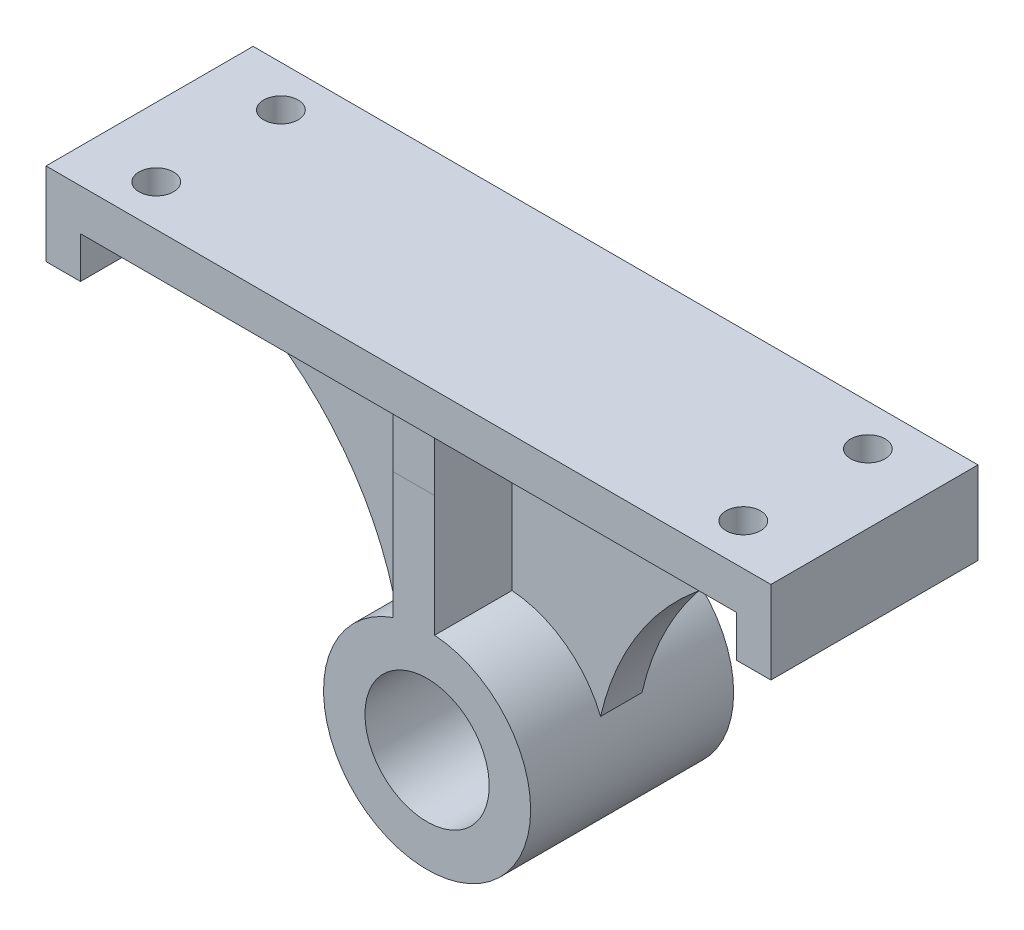
SolidWorks part; units mm, degrees
ref_plane "Front Plane" through (0, 0, 0) normal (0, 0, 1) x (1, 0, 0)
ref_plane "Top Plane" through (0, 0, 0) normal (0, 1, 0) x (1, 0, 0)
ref_plane "Right Plane" through (0, 0, 0) normal (1, 0, 0) x (0, 0, -1)
sketch "Sketch1" plane through (0, 0, 0) normal (0, 0, 1) x (1, 0, 0)
  line L0 (-266.7, 15.24) -> (-266.7, -45.72)
  line L1 (-241.3, -15.24) -> (241.3, -15.24)
  line L2 (-266.7, -15.24) -> (-266.7, 15.24)
  line L3 (-266.7, 15.24) -> (266.7, 15.24)
  line L4 (266.7, -15.24) -> (266.7, 15.24)
  line L7 (-266.7, -45.72) -> (-241.3, -45.72)
  line L8 (-241.3, -45.72) -> (-241.3, -15.24)
  line L9 (266.7, 15.24) -> (266.7, -45.72)
  line L10 (266.7, -45.72) -> (241.3, -45.72)
  line L11 (241.3, -45.72) -> (241.3, -15.24)
  point P0 (0, 0)
  dimension "D1" = 30.48
  dimension "D2" = 533.4
  dimension "D3" = 60.96
  dimension "D4" = 25.4
  dimension "D5" = 30.48
  dimension "D6" = 60.96
  dimension "D7" = 25.4
  dimension "D8" = 30.48
extrude "Boss-Extrude1" add sketch "Sketch1" against normal blind 152.4 contours L11 L10 L9 L4 L3 L0 L7 L8 L1 region at (0, -2.6504, 0)
sketch "Sketch3" plane through (0, 15.24, 0) normal (0, 1, 0) x (1, 0, 0)
  line L0 (-266.7, 0) -> (-215.9722, 0)
  line L1 (-266.7, 0) -> (266.7, 0) construction
  line L2 (-266.7, 152.4) -> (-266.7, 122.1057)
  line L3 (-266.7, 152.4) -> (-266.7, 0) construction
  line L4 (-266.7, 0) -> (-266.7, 30.4144)
  line L8 (0, 0) -> (0, 152.4) construction
  line L9 (-266.7, 152.4) -> (266.7, 152.4) construction
  circle A0 centre (-215.9722, 122.1057) radius 12.7
  circle A1 centre (-215.9722, 30.4144) radius 12.7
  circle A2 centre (215.9722, 30.4144) radius 12.7
  circle A3 centre (215.9722, 122.1057) radius 12.7
  point P23 (0, 0)
  point P24 (0, 0)
  dimension "D1" = 25.4
  dimension "D2" = 25.4
extrude "Cut-Extrude1" cut sketch "Sketch3" against normal blind 40.64 contours A3 | A2 | A0 | A1 region at (-215.9722, 15.24, -122.1057) region at (-215.9722, 15.24, -30.4144) region at (215.9722, 15.24, -30.4144) region at (215.9722, 15.24, -122.1057)
sketch "Sketch4" plane through (0, -15.24, 0) normal (0, -1, 0) x (1, 0, 0)
  line L0 (0, 0) -> (0, -152.4) construction
  line L1 (-182.88, -91.44) -> (182.88, -91.44)
  line L5 (-241.3, 0) -> (241.3, 0) construction
  line L6 (-241.3, -152.4) -> (241.3, -152.4) construction
  line L7 (0, -76.2) -> (0, -60.96)
  line L8 (0, -76.2) -> (0, -91.44)
  line L9 (-182.88, -60.96) -> (182.88, -60.96)
  line L11 (-182.88, -60.96) -> (-182.88, -91.44)
  line L12 (182.88, -60.96) -> (182.88, -91.44)
  dimension "D1" = 15.24
  dimension "D2" = 15.24
  dimension "D3" = 182.88
extrude "Boss-Extrude2" add sketch "Sketch4" along normal blind 40.64 contours L9 L11 L1 L8 L7 | L12 L9 L7 L8 L1 region at (-91.44, -15.24, -76.2) region at (91.44, -15.24, -76.2)
sketch "Sketch5" plane through (0, 0, -60.96) normal (0, 0, 1) x (1, 0, 0)
  line L2 (-15.24, -55.88) -> (-76.2, -55.88)
  line L5 (-182.88, -55.88) -> (-15.24, -55.88)
  line L12 (-15.24, -55.88) -> (15.24, -55.88)
  line L14 (15.24, -55.88) -> (15.24, -144.8495)
  line L15 (-15.24, -55.88) -> (-15.24, -148.8399)
  line L17 (15.24, -55.88) -> (182.88, -55.88)
  arc A0 (-15.24, -148.8399) -> (15.24, -144.8495) centre (9.6883, -220.847) ccw
  circle A1 centre (9.6883, -220.847) radius 45.72
  arc A2 (-64.5999, -237.8088) -> (-182.88, -55.88) centre (-277.9207, -247.0843) ccw
  arc A3 (80.423, -192.5089) -> (182.88, -55.88) centre (285.2269, -239.3595) cw
  point P0 (80.423, -192.5089)
  line M5 (-182.88, -55.88) -> (182.88, -55.88)
  dimension "D2" = 152.4
  dimension "D3" = 91.44
extrude "Boss-Extrude7" add sketch "Sketch5" against normal blind 30.48 contours A2 A0 L15 M5 | A0 A3 L14 M5 region at (-71.7998, -105.5302, -60.96) region at (75.3177, -102.0633, -60.96)
extrude "Boss-Extrude9" add sketch "Sketch5<16>" along normal mid plane 184.912 contours A1 | A0 L14 L12 L15
sketch "Sketch5<16>" plane through (0, 0, -60.96) normal (0, 0, 1) x (1, 0, 0) same geometry as "Sketch5"
sketch "Sketch9" plane through (0, -55.88, 0) normal (0, 1, 0) x (1, 0, 0)
  line L1 (106.297, -43.3341) -> (-99.7774, -43.3341)
  line L2 (106.297, -43.3341) -> (106.297, 4.0241)
  line L3 (106.297, 4.0241) -> (-99.7774, 4.0241)
  line L4 (-99.7774, -43.3341) -> (-99.7774, 4.0241)
  line L5 (106.297, -43.3341) -> (-99.7774, 4.0241) construction
  line L6 (106.297, 4.0241) -> (-99.7774, -43.3341) construction
  point P0 (3.2598, -19.655)
extrude "Cut-Extrude3" cut sketch "Sketch9" against normal blind 256.032
sketch "Sketch10" plane through (0, 0, -91.44) normal (0, 0, -1) x (-1, 0, 0)
  line L0 (0, -15.24) -> (0, -55.88)
  line L1 (182.88, -15.24) -> (-182.88, -15.24) construction
  line L2 (-15.1746, -55.88) -> (15.1746, -55.88)
  line L3 (15.1746, -55.88) -> (15.1746, -15.24)
  line L4 (15.1746, -15.24) -> (-15.1746, -15.24)
  line L5 (-15.1746, -55.88) -> (-15.1746, -15.24)
  line L6 (15.24, -55.88) -> (-15.24, -55.88) construction
  point P9 (0, -55.88)
  line M4 (182.88, -15.24) -> (-182.88, -15.24)
  line M9 (-15.24, -55.88) -> (15.24, -55.88)
extrude "Boss-Extrude10" add sketch "Sketch10" along normal blind 61.976 contours L5 L0 M9 M4 | L3 L0 M9 M4 region at (-7.5873, -35.56, -91.44) region at (7.5873, -35.56, -91.44)
sketch "Sketch11" plane through (0, 0, -60.96) normal (0, 0, 1) x (1, 0, 0)
  line L0 (0, -15.24) -> (0, -55.8923)
  line L1 (-182.88, -15.24) -> (182.88, -15.24) construction
  line L2 (0, -55.8923) -> (15.24, -55.88)
  line L3 (15.24, -55.88) -> (15.24, -15.24)
  line L4 (15.24, -15.24) -> (-15.24, -15.24)
  line L5 (0, -55.8923) -> (-15.24, -55.88)
  line L6 (-15.24, -55.88) -> (-15.24, -15.24)
  line M4 (182.88, -15.24) -> (-182.88, -15.24)
  line M9 (-15.24, -55.88) -> (15.24, -55.88)
extrude "Boss-Extrude11" add sketch "Sketch11" along normal blind 56.9346 contours L6 L0 M9 M4 | L3 L0 M9 M4 region at (7.62, -35.56, -60.96) region at (-7.62, -35.56, -60.96)
equation "\"2.2413.6in\"=2.2413"
